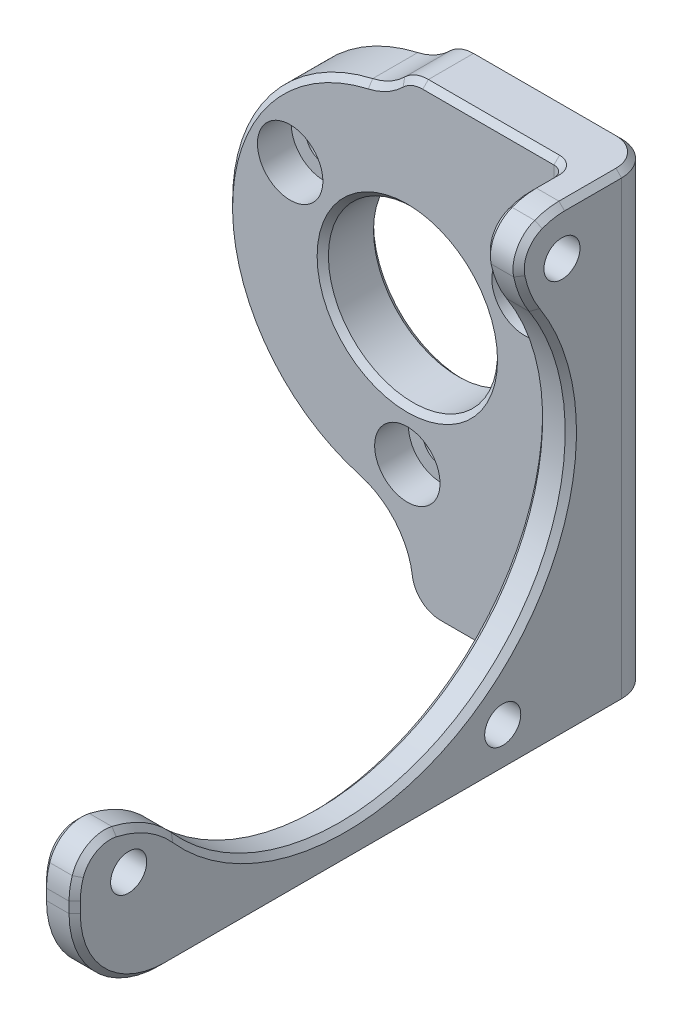
SolidWorks part; units mm, degrees
material "6061 合金"
ref_plane "前视基准面" through (0, 0, 0) normal (0, 0, 1) x (1, 0, 0)
ref_plane "上视基准面" through (0, 0, 0) normal (0, 1, 0) x (1, 0, 0)
ref_plane "右视基准面" through (0, 0, 0) normal (1, 0, 0) x (0, 0, -1)
other "Configuration Table"
sketch "草图1" plane through (0, 0, 0) normal (0, 0, 1) x (1, 0, 0)
  line L0 (-10.7623, 0) -> (8.7048, 0) construction
  line L1 (0, 6.2516) -> (0, -8.3883) construction
  circle A0 centre (0, 0) radius 16
  dimension "D1" = 32
extrude "凸台-拉伸1" add sketch "草图1" along normal blind 5
sketch "草图3" plane through (0, 0, 5) normal (0, 0, 1) x (1, 0, 0)
  circle A0 centre (0, 0) radius 12 construction
  point P0 (0, 12)
  point P12 (10.3923, -6)
  point P13 (-10.3923, -6)
  dimension "D1" = 24
  dimension "D2" = 3
hole_wizard "Ø3.0mm 暗销孔1" positions "草图3" profile "草图4" hole size "Ø3.0" standard "GB"
sketch "草图4" plane through (0, 12, 5) normal (1, 0, 0) x (0, -1, 0)
  line L0 (0, 0) -> (0, 3.9013)
  line L1 (0, 3.9013) -> (1.5, 3)
  line L2 (1.5, 3) -> (1.5, 0)
  line L5 (1.5, 0) -> (0, 0)
  line L10 (0, 3.9013) -> (-1.5, 3) construction
  line L11 (0, -6.35) -> (0, 107.95) construction
  dimension "孔直径" = 3
  dimension "孔深度" = 3
  dimension "导头角度" = 118
sketch "草图6" plane through (0, 0, 0) normal (0, 0, -1) x (-1, 0, 0)
  circle A0 centre (0, 0) radius 12 construction
  point P0 (0, -12)
  point P13 (-10.3923, 6)
  point P14 (10.3923, 6)
  dimension "D1" = 24
  dimension "D2" = 3
hole_wizard "孔1" positions "草图6" profile "草图7" legacy end condition through all
sketch "草图7" plane through (0, -12, 0) normal (1, 0, 0) x (0, 1, 0)
  line L0 (0, 0) -> (0, 5.9614)
  line L1 (0, 5.9614) -> (1.6, 5)
  line L2 (1.6, 5) -> (1.6, 3)
  line L3 (1.6, 3) -> (2.9, 3)
  line L4 (2.9, 0) -> (0, 0)
  line L5 (0, -11.3109) -> (0, 121.1557) construction
  line L6 (0, 5.9614) -> (-1.6, 5) construction
  line L7 (2.9, 3) -> (2.9, 0)
  dimension "直径" = 3.2
  dimension "深度" = 5
  dimension "柱坑直径" = 5.8
  dimension "柱坑深度" = 3
  dimension "导头角度" = 118
sketch "草图8" plane through (0, 0, 0) normal (0, 0, 1) x (1, 0, 0)
  line L0 (37.5243, 0) -> (-36.7763, 0) construction
  line L1 (0, 34.2207) -> (0, -32.974) construction
  line L2 (0, 23) -> (17, 23)
  line L3 (17, 23) -> (17, -23)
  line L4 (17, -23) -> (0, -23)
  line L5 (0, -23) -> (0, -16)
  line L6 (0, 23) -> (0, 16)
  circle A0 centre (0, 0) radius 16 construction
  arc A1 (0, -16) -> (0, 16) centre (0, 0) ccw
  dimension "D1" = 46
  dimension "D2" = 17
extrude "凸台-拉伸2" add sketch "草图8" along normal up to surface (5 mm away) up to face at (-1.6, -12, 5)
sketch "草图9" plane through (0, 0, 0) normal (0, 0, -1) x (-1, 0, 0)
  line L0 (-17, 23) -> (0, 23) construction
  line L1 (-17, -23) -> (-14, -23)
  line L2 (-17, -23) -> (-17, 23)
  line L3 (-17, 23) -> (-14, 23)
  line L4 (-14, -23) -> (-14, 23)
  dimension "D1" = 3
extrude "凸台-拉伸3" add sketch "草图9" along normal blind 46.5
sketch "草图12" plane through (17, 0, 0) normal (1, 0, 0) x (0, 0, -1)
  line L0 (46.5, 23) -> (46.5, -23) construction
  line L3 (-6.3808, 0) -> (22.5, 0) construction
  line L4 (22.5, 0) -> (3.2858, 13.9599) construction
  circle A0 centre (22.5, 0) radius 23.75 construction
  circle A1 centre (3.2858, 13.9599) radius 1.6
  circle A2 centre (36.4599, 19.2142) radius 1.6
  circle A3 centre (41.7142, -13.9599) radius 1.6
  circle A4 centre (8.5401, -19.2142) radius 1.6
  point P22 (22.5, 0)
  dimension "D2" = 47.5
  dimension "D4" = 3.2
  dimension "D1" = 24
  dimension "D3" = 36
  dimension "D5" = 4
extrude "切除-拉伸1" cut sketch "草图12" against normal blind 45
sketch "草图14" plane through (17, 0, 0) normal (1, 0, 0) x (0, 0, -1)
  line L0 (7.2858, 23) -> (7.2858, 16.2557)
  line L1 (-5, 23) -> (46.5, 23) construction
  line L2 (46.5, -9.9599) -> (44.8965, -9.9599)
  line L3 (46.5, 23) -> (46.5, -23) construction
  line L4 (7.2858, 23) -> (46.5, 23)
  line L5 (46.5, 23) -> (46.5, -9.9599)
  arc A0 (5.6906, 10.8371) -> (37.431, -13.3066) centre (22.5, 0) ccw
  circle A1 centre (3.2858, 13.9599) radius 1.6 construction
  circle A2 centre (41.7142, -13.9599) radius 1.6 construction
  arc A3 (44.8965, -9.9599) -> (37.431, -13.3066) centre (44.8965, -19.9599) ccw
  arc A4 (7.2858, 16.2557) -> (5.6906, 10.8371) centre (-2.7142, 16.2557) cw
  dimension "D1" = 40
  dimension "D4" = 10
  dimension "D2" = 4
  dimension "D3" = 4
extrude "切除-拉伸2" cut sketch "草图14" against normal through all
sketch "草图17" plane through (0, 0, 5) normal (0, 0, 1) x (1, 0, 0)
  line L0 (0, 23) -> (0, 16) construction
  line L1 (0, 18) -> (28.4206, 18)
  line L2 (0, 18) -> (0, 23)
  line L3 (0, 23) -> (28.4206, 23)
  line L4 (28.4206, 18) -> (28.4206, 23)
  line L5 (17, 23) -> (0, 23) construction
  dimension "D1" = 5
extrude "切除-拉伸3" cut sketch "草图17" against normal through all
fillet "圆角3" radius 6 4 edges at (15.5, -9.9599, -46.5) (15.5, 18, -7.2858) (0, -16, 2.5) (0, 16, 2.5)
fillet "圆角4" radius 3 5 edges at (17, -2.5, 5) (15.5, -9.9599, -44.8965) (0, -23, 2.5) (0, 18, 2.5) (15.5, 16.2557, -7.2858)
fillet "圆角5" radius 1 1 edges at (14, -2.5, 0)
fillet "圆角6" radius 8 1 edges at (15.5, -23, -46.5)
mirror "镜向1" about plane through (0, 0, 5) normal (0, 0, 1) of bodies 115
sketch "草图18" plane through (0, 0, 0) normal (0, 1, 0) x (1, 0, 0)
  line L0 (1.3696, -5) -> (14, -5) construction
  line L1 (-32.5584, -5) -> (28.1336, -5)
  line L2 (-32.5584, -5) -> (-32.5584, 53.8697)
  line L3 (-32.5584, 53.8697) -> (28.1336, 53.8697)
  line L4 (28.1336, -5) -> (28.1336, 53.8697)
extrude "切除-拉伸4" cut sketch "草图18" against normal through all both and the other way through all
sketch "草图19" plane through (0, 0, 10) normal (0, 0, 1) x (1, 0, 0)
  circle A0 centre (0, 0) radius 7.5
  dimension "D1" = 15
extrude "切除-拉伸5" cut sketch "草图19" against normal through all
chamfer "倒角1" distance 0.5 angle 45 42 edges at (14, -14.5215, 56.5) (14, -20.6569, 54.1569) (14, -13.1201, 56.4286) (14, -23, 29.75) (14, -10.5279, 54.8492) (13.7071, -23, 10.2929) (14, -11.3431, 49.822) (7.9621, -23, 10) (14, -15.9182, 20.3917) (0.945, -22.2546, 10) (14, 12.4441, 16.5309) (-1.4586, -17.2448, 10) (14, 16.2309, 16.7697) (-15.9948, 0.4081, 10) (14, 17.8992, 14.1512) (-2.0419, 16.1759, 10) (14, 18, 12.0281) (0.2392, 17.7789, 10) (13.7071, 18, 10.2929) (7.1848, 18, 10) (17, -14.5215, 56.5) (17, -20.6569, 54.1569) (17, -13.1201, 56.4286) (17, -23, 28.25) (17, -10.5279, 54.8492) (16.1213, -23, 5.8787) (17, -11.3431, 49.822) (8.4621, -23, 5) (17, -15.9182, 20.3917) (0.945, -22.2546, 5) (17, 12.4441, 16.5309) (-1.4586, -17.2448, 5) (17, 16.2309, 16.7697) (-15.9948, 0.4081, 5) (17, 17.8992, 14.1512) (-2.0419, 16.1759, 5) (17, 18, 10.5281) (0.2392, 17.7789, 5) (16.1213, 18, 5.8787) (7.6848, 18, 5) (7.5, 0, 10) (7.5, 0, 5)
